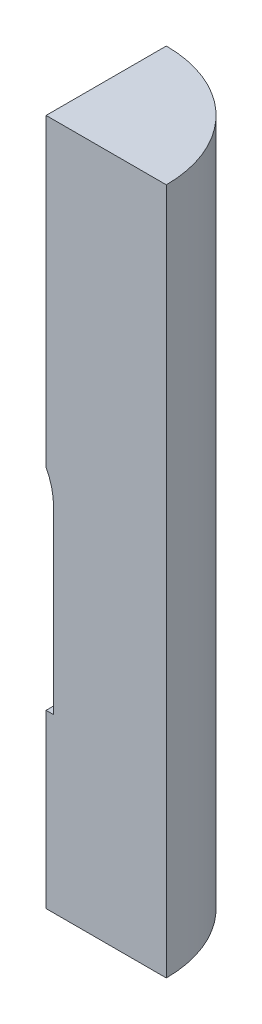
SolidWorks part; units mm, degrees
ref_plane "Front Plane" through (0, 0, 0) normal (0, 0, 1) x (1, 0, 0)
ref_plane "Top Plane" through (0, 0, 0) normal (0, 1, 0) x (1, 0, 0)
ref_plane "Right Plane" through (0, 0, 0) normal (1, 0, 0) x (0, 0, -1)
sketch "Sketch1" plane through (0, 0, 0) normal (0, 1, 0) x (1, 0, 0)
  line L0 (700, 0) -> (0, 0)
  line L1 (0, 0) -> (0, 700)
  arc A0 (700, 0) -> (0, 700) centre (0, 0) ccw
  dimension "D1" = 700
extrude "Inlet Section" add sketch "Sketch1" along normal blind 3000
extrude "Outlet Section" add sketch "Sketch1<2>" against normal blind 1000
sketch "Sketch1<2>" plane through (0, 0, 0) normal (0, 1, 0) x (1, 0, 0) same geometry as "Sketch1"
sketch "Sketch2" plane through (0, 0, 0) normal (0, 0, 1) x (1, 0, 0)
  line L0 (0, 0) -> (43.5, 0)
  line L1 (43.5, 0) -> (43.5, 1050)
  line L2 (0, 3000) -> (0, -1000) construction
  line L3 (0, 1225) -> (0, 0)
  arc A0 (43.5, 1050) -> (0, 1225) centre (-330.2615, 1050) ccw
  dimension "D1" = 43.5
  dimension "D2" = 1050
  dimension "D3" = 175
revolve "Rocket Body" cut sketch "Sketch2" angle 360 about L3
ref_plane "Plane1" through (0, 0, 0) normal (0.7071, 0, -0.7071) x (-0.7071, 0, -0.7071)
sketch "Sketch4" plane through (0, 0, 0) normal (0.7071, 0, -0.7071) x (-0.7071, 0, -0.7071)
  line L0 (0, 0) -> (0, 190) construction
  line L1 (0, 0) -> (4, 0) construction
  line L2 (4, 0) -> (4, 190) construction
  line L3 (4, 190) -> (0, 190) construction
  line L4 (4, 45) -> (4, 155)
  line L5 (1, 0) -> (-1, 0)
  line L6 (-4, 45) -> (-4, 155)
  spline S0 degree 3 poles (0, 190) (4, 190) (3.5559, 173.3734) (4, 155) knots 0 0 0 0 1 1 1 1
  spline S1 degree 3 poles (1, 0) (3.1567, 16.8638) (3.7296, 30.4146) (4, 45) knots 0 0 0 0 1 1 1 1
  spline S2 degree 3 poles (0, 190) (-4, 190) (-3.5559, 173.3734) (-4, 155) knots 0 0 0 0 1 1 1 1
  spline S3 degree 3 poles (-1, 0) (-3.1567, 16.8638) (-3.7296, 30.4146) (-4, 45) knots 0 0 0 0 1 1 1 1
  dimension "D1" = 190
  dimension "D2" = 4
  dimension "D3" = 1
  dimension "D4" = 45
  dimension "D5" = 35
ref_plane "Plane2" through (148.4924, 0, -148.4924) normal (0.7071, 0, -0.7071) x (-0.7071, 0, -0.7071)
sketch "Sketch5" plane through (148.4924, 0, -148.4924) normal (0.7071, 0, -0.7071) x (-0.7071, 0, -0.7071)
  line L0 (0, 0) -> (0, 135) construction
  line L1 (0, 0) -> (0, 190) construction
  line L2 (0, 135) -> (4, 135) construction
  line L3 (4, 135) -> (4, 0) construction
  line L4 (4, 0) -> (0, 0) construction
  line L5 (4, 0) -> (4, 190) construction
  line L6 (4, 45) -> (4, 155) construction
  line L7 (1, 0) -> (-1, 0)
  line L8 (4, 100) -> (4, 45)
  line L9 (-4, 100) -> (-4, 45)
  spline S0 degree 3 poles (1, 0) (2.8064, 15.5692) (3.9467, 29.595) (4, 45) knots 0 0 0 0 1 1 1 1
  spline S1 degree 3 poles (0, 135) (4, 135) (4, 117.5) (4, 100) knots 0 0 0 0 1 1 1 1
  spline S2 degree 3 poles (-1, 0) (-2.8064, 15.5692) (-3.9467, 29.595) (-4, 45) knots 0 0 0 0 1 1 1 1
  spline S3 degree 3 poles (0, 135) (-4, 135) (-4, 117.5) (-4, 100) knots 0 0 0 0 1 1 1 1
  dimension "D1" = 135
  dimension "D2" = 35
loft "Fin" cut profiles "Sketch5", "Sketch4"
